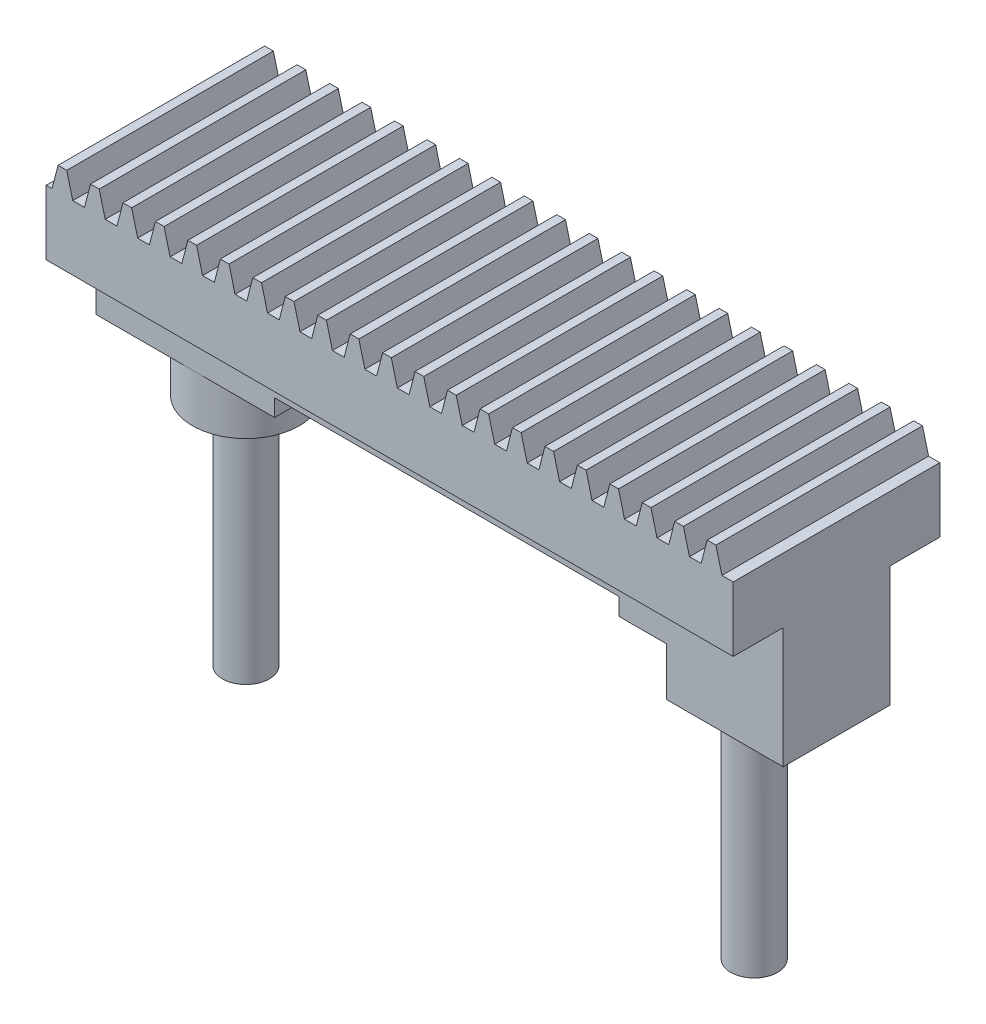
SolidWorks part; units mm, degrees
extrude "Blank" add sketch "BlankSke" against normal blind 20
sketch "BlankSke" plane through (0, 0, 0) normal (0, 0, 1) x (1, 0, 0)
  line L1 (0, 0) -> (100, 0)
  line L2 (0, 0) -> (0, 12.75)
  line L3 (0, 12.75) -> (100, 12.75)
  line L4 (100, 0) -> (100, 12.75)
  dimension "Length" = 100
ref_plane "Plane1" through (0, 0, 0) normal (0, 0, 1) x (1, 0, 0)
ref_plane "Plane2" through (0, 0, 0) normal (0, 1, 0) x (1, 0, 0)
ref_plane "Plane3" through (0, 0, 0) normal (1, 0, 0) x (0, 0, -1)
other "Configuration Table"
sketch "HoldingSke" plane through (0, 0, 0) normal (0, 1, 0) x (1, 0, 0)
  line L0 (0, 0) -> (0.0928, 0.6602)
  line L1 (-15, 0) -> (100, 0) construction
  line L2 (0, 0) -> (-2.1039, 2.3779)
  line L3 (0, 0) -> (-11.863, 4.5341)
  line L4 (0, 0) -> (7.9495, 3.3743)
  line L5 (0, 0) -> (-23.7986, -8.8762)
  line L6 (0, 0) -> (-10.5278, -7.1032)
  line L9 (-67.7845, 28.3722) -> (29.0302, 53.4102)
  line L10 (-76.2, 3.8779) -> (-64.95, 3.8779)
  line L11 (0, 0) -> (-20, 0)
  line L12 (-76.2, 101.6) -> (-76.147, 101.6)
  line L13 (24.9733, 27.94) -> (52.9518, 28.4284)
  line L14 (24.9733, 27.94) -> (24.9743, 27.94)
  line L15 (24.9733, 27.94) -> (100.4006, 29.5858)
  circle A0 centre (0, 0) radius 19.05
  circle A1 centre (0, 0) radius 5.625
  circle A2 centre (0, 0) radius 12.7
  dimension "Num_teeth" = 23
  dimension "Width" = 20
  dimension "Length" = 100
  dimension "Pitch_height" = 11.25
sketch "TooCutSkeIll" plane through (0, 0, 0) normal (0, 0, 1) x (1, 0, 0)
  line L0 (-1.7134, 12.705) -> (-0.9251, 9.6569)
  line L1 (-0.5611, 9.375) -> (0.5611, 9.375)
  line L2 (0.9251, 9.6569) -> (1.7134, 12.705)
  line L3 (100, 12.75) -> (0, 12.75) construction
  line L4 (0, 0) -> (0, 64.897) construction
  line L5 (-13.208, 11.25) -> (12.954, 11.25) construction
  line L6 (0, 0) -> (100, 0) construction
  line L7 (1.3371, 11.25) -> (1.3371, 48.7463) construction
  line L8 (-1.3371, 11.25) -> (-1.3371, 48.7463) construction
  line L9 (1.7715, 12.75) -> (1.7715, 12.7754)
  line L10 (-1.7715, 12.75) -> (-1.7715, 12.7754)
  line L11 (-1.7715, 12.7754) -> (1.7715, 12.7754)
  arc A0 (0.5611, 9.375) -> (0.9251, 9.6569) centre (0.5611, 9.751) ccw
  arc A1 (-0.9251, 9.6569) -> (-0.5611, 9.375) centre (-0.5611, 9.751) ccw
  arc A2 (1.7715, 12.75) -> (1.7134, 12.705) centre (1.7715, 12.69) ccw
  arc A3 (-1.7134, 12.705) -> (-1.7715, 12.75) centre (-1.7715, 12.69) ccw
  dimension "Addendum_plus" = 1.5254
  dimension "Pitch_height" = 11.25
  dimension "Pressure_angle" = 14.5
  dimension "Gap_width" = 2.6742
  dimension "Dedendum" = 1.875
extrude "ToothCutIll" [suppressed] cut sketch "TooCutSkeIll" against normal through all
sketch "TooCutSkeSim" plane through (0, 0, 0) normal (0, 0, 1) x (1, 0, 0)
  line L0 (0.8522, 9.375) -> (-0.8522, 9.375)
  line L1 (1.7316, 12.7754) -> (0.8522, 9.375)
  line L2 (0, 17.4625) -> (0, 53.467) construction
  line L3 (1.7316, 12.7754) -> (-1.7316, 12.7754)
  line L6 (-1.7316, 12.7754) -> (-0.8522, 9.375)
  line L9 (-1.3371, 11.25) -> (1.3371, 11.25) construction
  line L10 (0, 0) -> (100, 0) construction
  line L11 (1.3371, 11.25) -> (1.3371, 53.467) construction
  line L12 (-1.3371, 11.25) -> (-1.3371, 53.467) construction
  dimension "Addendum_plus" = 1.5254
  dimension "Pitch_height" = 11.25
  dimension "Pressure_angle" = 14.5
  dimension "Gap_width" = 2.6742
  dimension "Dedendum" = 1.875
extrude "ToothCutSim" cut sketch "TooCutSkeSim" against normal through all
pattern_linear "TeethCuts" count 23 spacing 4.7124 along (1, 0, 0) of "ToothCutIll", "ToothCutSim"
sketch "Croquis1" plane through (0, 0, 0) normal (0, 0, 1) x (1, 0, 0)
  line L89 (99.8124, 9.375) -> (98.108, 9.375)
  line L90 (98.108, 9.375) -> (97.2351, 12.75)
  line L91 (97.2351, 12.75) -> (95.9728, 12.75)
  line L92 (95.9728, 12.75) -> (95.1, 9.375)
  line L93 (95.1, 9.375) -> (93.3956, 9.375)
  line L94 (93.3956, 9.375) -> (92.5228, 12.75)
  line L95 (92.5228, 12.75) -> (91.2604, 12.75)
  line L96 (91.2604, 12.75) -> (90.3876, 9.375)
  line L97 (90.3876, 9.375) -> (88.6832, 9.375)
  line L98 (88.6832, 9.375) -> (87.8104, 12.75)
  line L99 (87.8104, 12.75) -> (86.548, 12.75)
  line L100 (86.548, 12.75) -> (85.6752, 9.375)
  line L101 (85.6752, 9.375) -> (83.9708, 9.375)
  line L102 (83.9708, 9.375) -> (83.098, 12.75)
  line L103 (83.098, 12.75) -> (81.8356, 12.75)
  line L104 (81.8356, 12.75) -> (80.9628, 9.375)
  line L105 (80.9628, 9.375) -> (79.2584, 9.375)
  line L106 (79.2584, 9.375) -> (78.3856, 12.75)
  line L107 (78.3856, 12.75) -> (77.1232, 12.75)
  line L108 (77.1232, 12.75) -> (76.2504, 9.375)
  line L109 (76.2504, 9.375) -> (74.546, 9.375)
  line L110 (74.546, 9.375) -> (73.6732, 12.75)
  line L111 (73.6732, 12.75) -> (72.4109, 12.75)
  line L112 (72.4109, 12.75) -> (71.538, 9.375)
  line L113 (71.538, 9.375) -> (69.8336, 9.375)
  line L114 (69.8336, 9.375) -> (68.9608, 12.75)
  line L115 (68.9608, 12.75) -> (67.6985, 12.75)
  line L116 (67.6985, 12.75) -> (66.8256, 9.375)
  line L117 (66.8256, 9.375) -> (65.1213, 9.375)
  line L118 (65.1213, 9.375) -> (64.2484, 12.75)
  line L119 (64.2484, 12.75) -> (62.9861, 12.75)
  line L120 (62.9861, 12.75) -> (62.1132, 9.375)
  line L121 (62.1132, 9.375) -> (60.4089, 9.375)
  line L122 (60.4089, 9.375) -> (59.536, 12.75)
  line L123 (59.536, 12.75) -> (58.2737, 12.75)
  line L124 (58.2737, 12.75) -> (57.4009, 9.375)
  line L125 (57.4009, 9.375) -> (55.6965, 9.375)
  line L126 (55.6965, 9.375) -> (54.8236, 12.75)
  line L127 (54.8236, 12.75) -> (53.5613, 12.75)
  line L128 (53.5613, 12.75) -> (52.6885, 9.375)
  line L129 (52.6885, 9.375) -> (50.9841, 9.375)
  line L130 (50.9841, 9.375) -> (50.1113, 12.75)
  line L131 (50.1113, 12.75) -> (48.8489, 12.75)
  line L132 (48.8489, 12.75) -> (47.9761, 9.375)
  line L133 (47.9761, 9.375) -> (46.2717, 9.375)
  line L134 (46.2717, 9.375) -> (45.3989, 12.75)
  line L135 (45.3989, 12.75) -> (44.1365, 12.75)
  line L136 (44.1365, 12.75) -> (43.2637, 9.375)
  line L137 (43.2637, 9.375) -> (41.5593, 9.375)
  line L138 (41.5593, 9.375) -> (40.6865, 12.75)
  line L139 (40.6865, 12.75) -> (39.4241, 12.75)
  line L140 (39.4241, 12.75) -> (38.5513, 9.375)
  line L141 (38.5513, 9.375) -> (36.8469, 9.375)
  line L142 (36.8469, 9.375) -> (35.9741, 12.75)
  line L143 (35.9741, 12.75) -> (34.7117, 12.75)
  line L144 (34.7117, 12.75) -> (33.8389, 9.375)
  line L145 (33.8389, 9.375) -> (32.1345, 9.375)
  line L146 (32.1345, 9.375) -> (31.2617, 12.75)
  line L147 (31.2617, 12.75) -> (29.9994, 12.75)
  line L148 (29.9994, 12.75) -> (29.1265, 9.375)
  line L149 (29.1265, 9.375) -> (27.4221, 9.375)
  line L150 (27.4221, 9.375) -> (26.5493, 12.75)
  line L151 (26.5493, 12.75) -> (25.287, 12.75)
  line L152 (25.287, 12.75) -> (24.4141, 9.375)
  line L153 (24.4141, 9.375) -> (22.7098, 9.375)
  line L154 (22.7098, 9.375) -> (21.8369, 12.75)
  line L155 (21.8369, 12.75) -> (20.5746, 12.75)
  line L156 (20.5746, 12.75) -> (19.7017, 9.375)
  line L157 (19.7017, 9.375) -> (17.9974, 9.375)
  line L158 (17.9974, 9.375) -> (17.1245, 12.75)
  line L159 (17.1245, 12.75) -> (15.8622, 12.75)
  line L160 (15.8622, 12.75) -> (14.9894, 9.375)
  line L161 (14.9894, 9.375) -> (13.285, 9.375)
  line L162 (13.285, 9.375) -> (12.4121, 12.75)
  line L163 (12.4121, 12.75) -> (11.1498, 12.75)
  line L164 (11.1498, 12.75) -> (10.277, 9.375)
  line L165 (10.277, 9.375) -> (8.5726, 9.375)
  line L166 (8.5726, 9.375) -> (7.6998, 12.75)
  line L167 (7.6998, 12.75) -> (6.4374, 12.75)
  line L168 (6.4374, 12.75) -> (5.5646, 9.375)
  line L169 (5.5646, 9.375) -> (3.8602, 9.375)
  line L170 (3.8602, 9.375) -> (2.9874, 12.75)
  line L171 (2.9874, 12.75) -> (1.725, 12.75)
  line L172 (1.725, 12.75) -> (0.8522, 9.375)
  line L173 (0.8522, 9.375) -> (0, 9.375)
  line L174 (0, 9.375) -> (0, 0)
  line L175 (0, 0) -> (100, 0)
  line L176 (100, 0) -> (100, 10.1006)
  line L177 (100, 10.1006) -> (99.8124, 9.375)
  line L178 (99.8124, 9.375) -> (98.108, 9.375)
  line L179 (98.108, 9.375) -> (97.2351, 12.75)
  line L180 (97.2351, 12.75) -> (95.9728, 12.75)
  line L181 (95.9728, 12.75) -> (95.1, 9.375)
  line L182 (95.1, 9.375) -> (93.3956, 9.375)
  line L183 (93.3956, 9.375) -> (92.5228, 12.75)
  line L184 (92.5228, 12.75) -> (91.2604, 12.75)
  line L185 (91.2604, 12.75) -> (90.3876, 9.375)
  line L186 (90.3876, 9.375) -> (88.6832, 9.375)
  line L187 (88.6832, 9.375) -> (87.8104, 12.75)
  line L188 (87.8104, 12.75) -> (86.548, 12.75)
  line L189 (86.548, 12.75) -> (85.6752, 9.375)
  line L190 (85.6752, 9.375) -> (83.9708, 9.375)
  line L191 (83.9708, 9.375) -> (83.098, 12.75)
  line L192 (83.098, 12.75) -> (81.8356, 12.75)
  line L193 (81.8356, 12.75) -> (80.9628, 9.375)
  line L194 (80.9628, 9.375) -> (79.2584, 9.375)
  line L195 (79.2584, 9.375) -> (78.3856, 12.75)
  line L196 (78.3856, 12.75) -> (77.1232, 12.75)
  line L197 (77.1232, 12.75) -> (76.2504, 9.375)
  line L198 (76.2504, 9.375) -> (74.546, 9.375)
  line L199 (74.546, 9.375) -> (73.6732, 12.75)
  line L200 (73.6732, 12.75) -> (72.4109, 12.75)
  line L201 (72.4109, 12.75) -> (71.538, 9.375)
  line L202 (71.538, 9.375) -> (69.8336, 9.375)
  line L203 (69.8336, 9.375) -> (68.9608, 12.75)
  line L204 (68.9608, 12.75) -> (67.6985, 12.75)
  line L205 (67.6985, 12.75) -> (66.8256, 9.375)
  line L206 (66.8256, 9.375) -> (65.1213, 9.375)
  line L207 (65.1213, 9.375) -> (64.2484, 12.75)
  line L208 (64.2484, 12.75) -> (62.9861, 12.75)
  line L209 (62.9861, 12.75) -> (62.1132, 9.375)
  line L210 (62.1132, 9.375) -> (60.4089, 9.375)
  line L211 (60.4089, 9.375) -> (59.536, 12.75)
  line L212 (59.536, 12.75) -> (58.2737, 12.75)
  line L213 (58.2737, 12.75) -> (57.4009, 9.375)
  line L214 (57.4009, 9.375) -> (55.6965, 9.375)
  line L215 (55.6965, 9.375) -> (54.8236, 12.75)
  line L216 (54.8236, 12.75) -> (53.5613, 12.75)
  line L217 (53.5613, 12.75) -> (52.6885, 9.375)
  line L218 (52.6885, 9.375) -> (50.9841, 9.375)
  line L219 (50.9841, 9.375) -> (50.1113, 12.75)
  line L220 (50.1113, 12.75) -> (48.8489, 12.75)
  line L221 (48.8489, 12.75) -> (47.9761, 9.375)
  line L222 (47.9761, 9.375) -> (46.2717, 9.375)
  line L223 (46.2717, 9.375) -> (45.3989, 12.75)
  line L224 (45.3989, 12.75) -> (44.1365, 12.75)
  line L225 (44.1365, 12.75) -> (43.2637, 9.375)
  line L226 (43.2637, 9.375) -> (41.5593, 9.375)
  line L227 (41.5593, 9.375) -> (40.6865, 12.75)
  line L228 (40.6865, 12.75) -> (39.4241, 12.75)
  line L229 (39.4241, 12.75) -> (38.5513, 9.375)
  line L230 (38.5513, 9.375) -> (36.8469, 9.375)
  line L231 (36.8469, 9.375) -> (35.9741, 12.75)
  line L232 (35.9741, 12.75) -> (34.7117, 12.75)
  line L233 (34.7117, 12.75) -> (33.8389, 9.375)
  line L234 (33.8389, 9.375) -> (32.1345, 9.375)
  line L235 (32.1345, 9.375) -> (31.2617, 12.75)
  line L236 (31.2617, 12.75) -> (29.9994, 12.75)
  line L237 (29.9994, 12.75) -> (29.1265, 9.375)
  line L238 (29.1265, 9.375) -> (27.4221, 9.375)
  line L239 (27.4221, 9.375) -> (26.5493, 12.75)
  line L240 (26.5493, 12.75) -> (25.287, 12.75)
  line L241 (25.287, 12.75) -> (24.4141, 9.375)
  line L242 (24.4141, 9.375) -> (22.7098, 9.375)
  line L243 (22.7098, 9.375) -> (21.8369, 12.75)
  line L244 (21.8369, 12.75) -> (20.5746, 12.75)
  line L245 (20.5746, 12.75) -> (19.7017, 9.375)
  line L246 (19.7017, 9.375) -> (17.9974, 9.375)
  line L247 (17.9974, 9.375) -> (17.1245, 12.75)
  line L248 (17.1245, 12.75) -> (15.8622, 12.75)
  line L249 (15.8622, 12.75) -> (14.9894, 9.375)
  line L250 (14.9894, 9.375) -> (13.285, 9.375)
  line L251 (13.285, 9.375) -> (12.4121, 12.75)
  line L252 (12.4121, 12.75) -> (11.1498, 12.75)
  line L253 (11.1498, 12.75) -> (10.277, 9.375)
  line L254 (10.277, 9.375) -> (8.5726, 9.375)
  line L255 (8.5726, 9.375) -> (7.6998, 12.75)
  line L256 (7.6998, 12.75) -> (6.4374, 12.75)
  line L257 (6.4374, 12.75) -> (5.5646, 9.375)
  line L258 (5.5646, 9.375) -> (3.8602, 9.375)
  line L259 (3.8602, 9.375) -> (2.9874, 12.75)
  line L260 (2.9874, 12.75) -> (1.725, 12.75)
  line L261 (1.725, 12.75) -> (0.8522, 9.375)
  line L262 (0.8522, 9.375) -> (0, 9.375)
  line L263 (0, 9.375) -> (0, 0)
  line L264 (0, 0) -> (100, 0)
  line L265 (100, 0) -> (100, 10.1006)
  line L266 (100, 10.1006) -> (99.8124, 9.375)
  dimension "D1" = 0
extrude "Saliente-Extruir1" add sketch "Croquis1" along normal blind 10
sketch "Croquis12" plane through (100, 0, 0) normal (1, 0, 0) x (0, 0, -1)
  line L4 (20, 10.1006) -> (-10, 10.1006)
  line L5 (-10, 10.1006) -> (-10, 0)
  line L6 (-10, 0) -> (20, 0)
  line L7 (20, 0) -> (20, 10.1006)
  line L8 (20, 10.1006) -> (-10, 10.1006)
  line L9 (-10, 10.1006) -> (-10, 0)
  line L10 (-10, 0) -> (20, 0)
  line L11 (20, 0) -> (20, 10.1006)
  dimension "D1" = 0
extrude "Cortar-Extruir1" cut sketch "Croquis12" against normal blind 0.25 and the other way through all
ref_plane "Plano1" through (0, 0, -5) normal (0, 0, 1) x (1, 0, 0)
sketch "Croquis13" plane through (0, 0, 0) normal (0, -1, 0) x (1, 0, 0)
  line L0 (0, -5) -> (107.4582, -5) construction
  line L1 (0, 2.75) -> (99.75, 2.75)
  line L2 (99.75, 10) -> (99.75, -20) construction
  line L3 (99.75, 2.75) -> (99.75, -12.75)
  line L4 (0, -20) -> (99.75, -20)
  line L5 (99.75, -20) -> (99.75, 10)
  line L6 (99.75, 10) -> (0, 10)
  line L7 (0, 10) -> (0, -20)
  line L11 (0, 10) -> (0, -20) construction
  line L12 (0, 2.75) -> (0, -12.75)
  line L13 (0, -12.75) -> (99.75, -12.75)
  point P11 (99.75, -5)
  dimension "D2" = 7.75
  dimension "D1" = 0
extrude "Saliente-Extruir6" add sketch "Croquis13" along normal blind 10.5
sketch "Croquis14" plane through (0, -10.5, 0) normal (0, -1, 0) x (1, 0, 0)
  line L0 (0, -5) -> (108.0787, -5) construction
  line L4 (0, 2.75) -> (0, -12.75)
  line L5 (0, -12.75) -> (99.75, -12.75)
  line L6 (99.75, -12.75) -> (99.75, 2.75)
  line L7 (99.75, 2.75) -> (0, 2.75)
  line L8 (0, 2.75) -> (0, -12.75) construction
  line L9 (0, -12.75) -> (99.75, -12.75) construction
  line L10 (99.75, -12.75) -> (99.75, 2.75) construction
  line L11 (99.75, 2.75) -> (0, 2.75) construction
  circle A0 centre (14, -5) radius 3.4
  circle A1 centre (87.8, -5) radius 3.4
  circle A2 centre (14, -5) radius 7.75
  circle A3 centre (87.8, -5) radius 7.75
  dimension "D2" = 6.8
  dimension "D3" = 73.8
  dimension "D4" = 14
  dimension "D1" = 0
extrude "Saliente-Extruir7" add sketch "Croquis14" along normal blind 7
sketch "Croquis15" plane through (0, -10.5, 0) normal (0, -1, 0) x (1, 0, 0)
  circle A0 centre (87.8, -5) radius 3.4 construction
  circle A1 centre (14, -5) radius 3.4 construction
  circle A2 centre (87.8, -5) radius 3.4
  circle A3 centre (14, -5) radius 3.4
extrude "Saliente-Extruir8" add sketch "Croquis15" along normal blind 41
sketch "Croquis16" plane through (0, 0, 2.75) normal (0, 0, 1) x (1, 0, 0)
  line L0 (0.926, -3) -> (118.1708, -3) construction
  line L1 (46.2, -4.6) -> (46.2, -1.4)
  line L2 (34.2, -4.6) -> (28, -4.6)
  line L3 (34.2, -4.6) -> (34.2, -1.4)
  line L4 (34.2, -1.4) -> (28, -1.4)
  line L5 (28, -4.6) -> (28, -1.4)
  line L6 (99.75, 0) -> (0, 0)
  line L7 (0, 0) -> (0, -10.5)
  line L8 (0, -10.5) -> (14, -10.5)
  line L9 (14, -10.5) -> (87.8, -10.5)
  line L10 (87.8, -10.5) -> (99.75, -10.5)
  line L11 (99.75, -10.5) -> (99.75, 0)
  line L12 (99.75, 0) -> (0, 0) construction
  line L13 (0, 0) -> (0, -10.5) construction
  line L14 (0, -10.5) -> (14, -10.5) construction
  line L15 (14, -10.5) -> (87.8, -10.5) construction
  line L16 (87.8, -10.5) -> (99.75, -10.5) construction
  line L17 (99.75, -10.5) -> (99.75, 0) construction
  line L18 (34.2, -4.6) -> (28, -1.4) construction
  line L19 (34.2, -1.4) -> (28, -4.6) construction
  line L20 (46.2, -1.4) -> (40, -1.4)
  line L21 (40, -4.6) -> (40, -1.4)
  line L22 (46.2, -4.6) -> (40, -4.6)
  line L23 (58.2, -4.6) -> (58.2, -1.4)
  line L24 (58.2, -1.4) -> (52, -1.4)
  line L25 (52, -4.6) -> (52, -1.4)
  line L26 (58.2, -4.6) -> (52, -4.6)
  line L27 (70.2, -4.6) -> (70.2, -1.4)
  line L28 (70.2, -1.4) -> (64, -1.4)
  line L29 (64, -4.6) -> (64, -1.4)
  line L30 (70.2, -4.6) -> (64, -4.6)
  line L31 (82.2, -4.6) -> (82.2, -1.4)
  line L32 (82.2, -1.4) -> (76, -1.4)
  line L33 (76, -4.6) -> (76, -1.4)
  line L34 (82.2, -4.6) -> (76, -4.6)
  line L35 (94.2, -4.6) -> (94.2, -1.4)
  line L36 (94.2, -1.4) -> (88, -1.4)
  line L37 (88, -4.6) -> (88, -1.4)
  line L38 (94.2, -4.6) -> (88, -4.6)
  point P6 (31.1, -3)
  dimension "D2" = 7.5
  dimension "D3" = 28
  dimension "D4" = 6.2
  dimension "D5" = 3.2
  dimension "D1" = 0
  dimension "D6" = 6
sketch "Croquis17" plane through (0, -10.5, 0) normal (0, -1, 0) x (1, 0, 0)
  line L0 (14, -5) -> (87.8, -5) construction
  line L2 (25.9, 5.9202) -> (75.9, 5.9202)
  line L3 (25.9, 5.9202) -> (25.9, -15.9202)
  line L4 (25.9, -15.9202) -> (75.9, -15.9202)
  line L5 (75.9, 5.9202) -> (75.9, -15.9202)
  line L6 (25.9, 5.9202) -> (75.9, -15.9202) construction
  line L7 (25.9, -15.9202) -> (75.9, 5.9202) construction
  circle A0 centre (87.8, -5) radius 3.4 construction
  circle A1 centre (14, -5) radius 3.4 construction
  circle A2 centre (87.8, -5) radius 3.4 construction
  circle A3 centre (14, -5) radius 3.4 construction
  point P6 (50.9, -5)
  dimension "D1" = 50
extrude "Cortar-Extruir3" cut sketch "Croquis17" against normal blind 2.5
sketch "Croquis18" plane through (0, -17.5, 0) normal (0, -1, 0) x (1, 0, 0)
  circle A0 centre (87.8, -5) radius 3.4 construction
  circle A1 centre (87.8, -5) radius 7.75 construction
  circle A2 centre (87.8, -5) radius 3.4 construction
  circle A3 centre (87.8, -5) radius 7.75
  circle A4 centre (87.8, -5) radius 3.4
  dimension "D1" = 6.8
extrude "Cortar-Extruir4" cut sketch "Croquis18" against normal up to surface (7 mm away) up to face at (95.7125, -10.5, -5)
sketch "Croquis19" plane through (0, -10.5, 0) normal (0, -1, 0) x (1, 0, 0)
  line L0 (82.8, 2.75) -> (82.8, -12.75)
  line L1 (99.75, 2.75) -> (75.9, 2.75) construction
  line L2 (75.9, -12.75) -> (99.75, -12.75) construction
  line L3 (82.8, 2.75) -> (99.75, 2.75)
  line L4 (99.75, 2.75) -> (99.75, -12.75)
  line L5 (99.75, -12.75) -> (82.8, -12.75)
  line L6 (99.75, -12.75) -> (99.75, 2.75) construction
  circle A0 centre (87.8, -5) radius 3.4 construction
  circle A1 centre (87.8, -5) radius 3.4 construction
  dimension "D1" = 5
extrude "Saliente-Extruir9" add sketch "Croquis19" along normal blind 7
equation "' \"Module@HoldingSke\" = 6.35"
equation "' \"Num_teeth@HoldingSke\" = 12"
equation "' \"Ap@HoldingSke\" =  20"
equation "' \"Ap@HoldingSke\" = 20"
equation "' \"Width@HoldingSke\" = 0.25 * 25.4"
equation "' \"Show_teeth@HoldingSke\" = 500"
equation "' \"Backlash@HoldingSke\" = 0.009 * 25.4"
equation "' \"Addendum_fac@HoldingSke\" = 1.0"
equation "' \"Dedendum_fac@HoldingSke\" = 1.25"
equation "' \"Dedendum_add@HoldingSke\" = 0.00005 * 25.4"
equation "' \"Clearance_fac@HoldingSke\" = 0.25"
equation "' \"Pitch_height@HoldingSke\" = 1 * 25.4"
equation "' \"Length@HoldingSke\" = 4.71 * 25.4"
equation "\"Pitch@HoldingSke\" = 1 / \"Module@HoldingSke\""
equation "\"MPH@HoldingSke\" = \"Dedendum_fac@HoldingSke\" / \"Pitch@HoldingSke\" + 2 * \"Dedendum_add@HoldingSke\" + 0.002 * 25.4"
equation "\"MPH@HoldingSke\" = ((sgn( \"MPH@HoldingSke\" - \"Pitch_height@HoldingSke\")+1)*( \"MPH@HoldingSke\" - \"Pitch_height@HoldingSke\"))/2 + \"Pitch_height@HoldingSke\""
equation "\"Blank_height@BlankSke\" = \"Pitch_height@HoldingSke\" + \"Addendum_fac@HoldingSke\"  / \"Pitch@HoldingSke\" "
equation "\"Length@BlankSke\" =  \"Length@HoldingSke\""
equation "\"Face_width@Blank\" = \"Width@HoldingSke\""
equation "\"Pressure_angle@TooCutSkeIll\" = \"Ap@HoldingSke\""
equation "\"Addendum_plus@TooCutSkeIll\" =  \"Addendum_fac@HoldingSke\"  / \"Pitch@HoldingSke\" + 0.001 *25.4"
equation "\"Dedendum@TooCutSkeIll\" = \"Dedendum_fac@HoldingSke\"  / \"Pitch@HoldingSke\""
equation "\"Pitch_height@TooCutSkeIll\" =  \"MPH@HoldingSke\""
equation "\"Gap_width@TooCutSkeIll\" = 3.14159265 / 2 / \"Pitch@HoldingSke\" + 6 * \"Backlash@HoldingSke\""
equation "\"Pressure_angle@TooCutSkeSim\" = \"Ap@HoldingSke\""
equation "\"Addendum_plus@TooCutSkeSim\" =  \"Addendum_fac@HoldingSke\"  / \"Pitch@HoldingSke\" + 0.001 * 25.4"
equation "\"Dedendum@TooCutSkeSim\" = \"Dedendum_fac@HoldingSke\"  / \"Pitch@HoldingSke\""
equation "\"Pitch_height@TooCutSkeSim\" =  \"MPH@HoldingSke\""
equation "\"Gap_width@TooCutSkeSim\" = 3.14159265 / 2 / \"Pitch@HoldingSke\" + 6 * \"Backlash@HoldingSke\""
equation "\"Root_fillet@TooCutSkeIll\" = \"Clearance_fac@HoldingSke\" / \"Pitch@HoldingSke\" + \"Dedendum_add@HoldingSke\""
equation "\"Break_rad@TooCutSkeIll\" = 0.02 / \"Pitch@HoldingSke\" * 2"
equation "\"Linear_pitch@TeethCuts\" = 3.14159265 / \"Pitch@HoldingSke\""
equation "\"Num_teeth@HoldingSke\" = int( ( \"Length@HoldingSke\" + 0 ) / (3.14159265 / \"Pitch@HoldingSke\")) + 0.9999  + 1"
equation " \"Num_teeth@TeethCuts\" = int( \"Show_teeth@HoldingSke\" ) + 1"
equation " \"Num_teeth@TeethCuts\" = ((sgn( \"Num_teeth@TeethCuts\" - \"Num_teeth@HoldingSke\" )-1)*( \"Num_teeth@TeethCuts\" - \"Num_teeth@HoldingSke\" ))/-2+ \"Num_teeth@HoldingSke\""
equation " \"Num_teeth@TeethCuts\" = ((sgn( \"Num_teeth@TeethCuts\" - 2.0)+1)*( \"Num_teeth@TeethCuts\" - 2.0))/2 +2.0"
